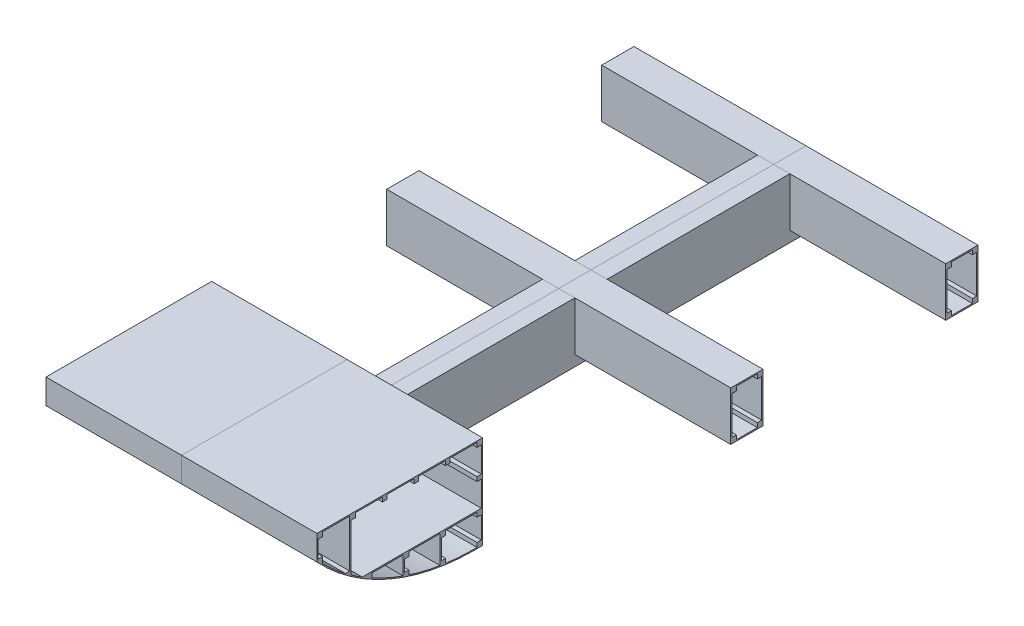
SolidWorks part; units mm, degrees
ref_plane "Front Plane" through (0, 0, 0) normal (0, 0, 1) x (1, 0, 0)
ref_plane "Top Plane" through (0, 0, 0) normal (0, 1, 0) x (1, 0, 0)
ref_plane "Right Plane" through (0, 0, 0) normal (1, 0, 0) x (0, 0, -1)
sketch "Sketch1" plane through (0, 0, 0) normal (1, 0, 0) x (0, 0, -1)
  line L0 (5334, 765) -> (5334, 309) construction
  line L1 (5184, 765) -> (5484, 765)
  line L2 (5184, 765) -> (5184, 309)
  line L3 (5184, 309) -> (5484, 309)
  line L4 (5484, 765) -> (5484, 309)
  line L5 (7184, 765) -> (7484, 765)
  line L6 (7184, 765) -> (7184, 309)
  line L7 (7184, 309) -> (7484, 309)
  line L8 (7484, 765) -> (7484, 309)
  line L9 (7184, 537) -> (7484, 537) construction
  line L10 (5184, 537) -> (5484, 537) construction
  line L11 (7334, 765) -> (7334, 309) construction
  line L12 (7432, 753) -> (7236, 753)
  line L13 (7236, 753) -> (7236, 713)
  line L14 (7236, 713) -> (7196, 713)
  line L15 (7196, 713) -> (7196, 361)
  line L16 (5432, 753) -> (5236, 753)
  line L17 (5236, 753) -> (5236, 713)
  line L18 (5236, 713) -> (5196, 713)
  line L19 (5196, 713) -> (5196, 361)
  line L20 (5472, 713) -> (5472, 361)
  line L21 (5432, 713) -> (5472, 713)
  line L22 (5432, 753) -> (5432, 713)
  line L23 (5236, 361) -> (5196, 361)
  line L24 (5236, 321) -> (5236, 361)
  line L25 (5432, 321) -> (5236, 321)
  line L26 (5432, 321) -> (5432, 361)
  line L27 (5432, 361) -> (5472, 361)
  line L28 (7472, 713) -> (7472, 361)
  line L29 (7432, 713) -> (7472, 713)
  line L30 (7432, 753) -> (7432, 713)
  line L31 (7236, 361) -> (7196, 361)
  line L32 (7236, 321) -> (7236, 361)
  line L33 (7432, 321) -> (7236, 321)
  line L34 (7432, 321) -> (7432, 361)
  line L35 (7432, 361) -> (7472, 361)
  line L36 (7500.6785, 309) -> (3141.2111, 309) construction
  line L37 (5184, 758.7422) -> (5184, 309) construction
  line L38 (5184, 765) -> (7500, 765) construction
  line L39 (7500.4262, 765) -> (5543.6931, 765) construction
  line L40 (7484, 759) -> (7484, -100) construction
  point P30 (5334, 753)
  point P31 (5196, 537)
  point P36 (5472, 537)
  point P37 (0, 0)
  point P40 (7334, 753)
  point P41 (7196, 537)
  point P46 (7472, 537)
  point P51 (7464.8091, 765)
  dimension "D1" = 12
  dimension "D2" = 12
  dimension "D3" = 40
  dimension "D4" = 12
  dimension "D5" = 300
  dimension "D7" = 1700
extrude "Boss-Extrude1" add sketch "Sketch1" along normal blind 1600
sketch "Sketch3" plane through (0, 0, 0) normal (1, 0, 0) x (0, 0, -1)
  line L0 (1675, 1176.9786) -> (3216, 1176.9786)
  line L1 (3216, 309) -> (3216, 1205.7293) construction
  line L2 (3216, 1176.9786) -> (3216, 309)
  line L3 (3216, 309) -> (3141.2111, 309)
  line L4 (1675, 1176.9786) -> (1675, 946.193)
  line L5 (3164, 1164.9786) -> (3164, 1124.9786)
  line L6 (3164, 1124.9786) -> (3204, 1124.9786)
  line L7 (3204, 1124.9786) -> (3204, 889.9786)
  line L8 (3204, 889.9786) -> (3164, 889.9786)
  line L9 (3164, 889.9786) -> (3164, 849.9786)
  line L10 (3164, 849.9786) -> (3204, 849.9786)
  line L11 (3204, 849.9786) -> (3204, 614.9786)
  line L12 (3204, 614.9786) -> (2096.401, 614.9786)
  line L13 (3164, 1164.9786) -> (2911, 1164.9786)
  line L14 (2911, 1164.9786) -> (2911, 1124.9786)
  line L15 (2911, 1124.9786) -> (2871, 1124.9786)
  line L16 (2871, 1124.9786) -> (2871, 1164.9786)
  line L17 (2871, 1164.9786) -> (2618, 1164.9786)
  line L18 (2618, 1164.9786) -> (2618, 1124.9786)
  line L19 (2618, 1124.9786) -> (2578, 1124.9786)
  line L20 (2578, 1124.9786) -> (2578, 1164.9786)
  line L21 (2578, 1164.9786) -> (2325, 1164.9786)
  line L22 (2325, 1164.9786) -> (2325, 1124.9786)
  line L23 (2325, 1124.9786) -> (2285, 1124.9786)
  line L24 (2285, 1124.9786) -> (2285, 1164.9786)
  line L25 (2285, 1164.9786) -> (2032, 1164.9786)
  line L26 (2032, 1164.9786) -> (2032, 1124.9786)
  line L27 (2032, 1124.9786) -> (1992, 1124.9786)
  line L29 (1980, 1164.9786) -> (1727, 1164.9786)
  line L30 (1727, 1164.9786) -> (1727, 1124.9786)
  line L31 (1727, 1124.9786) -> (1687, 1124.9786)
  line L32 (1687, 1124.9786) -> (1687, 964.9786)
  line L33 (1687, 964.9786) -> (1727, 964.9786)
  line L34 (1727, 964.9786) -> (1727, 907.371)
  line L35 (3164, 602.9786) -> (2872.7112, 602.9786)
  line L36 (2872.7112, 602.9786) -> (2872.7112, 562.9786)
  line L37 (2872.7112, 562.9786) -> (2832.7112, 562.9786)
  line L38 (2832.7112, 562.9786) -> (2832.7112, 377.6578)
  line L39 (2832.7112, 377.6578) -> (2872.7112, 377.6578)
  line L40 (2872.7112, 377.6578) -> (2872.7112, 337.6578)
  line L41 (3164, 602.9786) -> (3164, 562.9786)
  line L42 (3164, 562.9786) -> (3204, 562.9786)
  line L43 (3204, 562.9786) -> (3204, 359.6372)
  line L44 (3204, 359.6372) -> (3164, 359.6372)
  line L45 (3164, 359.6372) -> (3164, 319.6372)
  line L46 (2820.7112, 602.9786) -> (2820.7112, 345.4198)
  line L47 (2820.7112, 602.9786) -> (2529.4224, 602.9786)
  line L48 (2529.4224, 602.9786) -> (2529.4224, 562.9786)
  line L49 (2529.4224, 562.9786) -> (2489.4224, 562.9786)
  line L50 (2489.4224, 562.9786) -> (2489.4224, 455.6286)
  line L51 (2489.4224, 455.6286) -> (2529.4224, 455.6286)
  line L52 (2529.4224, 455.6286) -> (2529.4224, 415.6286)
  line L53 (2477.4224, 433.1752) -> (2477.4224, 602.9786)
  line L54 (2477.4224, 602.9786) -> (2186.1335, 602.9786)
  line L55 (2186.1335, 602.9786) -> (2186.1335, 562.9786)
  line L56 (1980, 1164.9786) -> (1980, 721.6741)
  line L57 (1980, 721.6741) -> (1940, 721.6741)
  line L58 (1992, 1124.9786) -> (1992, 683.7591)
  arc A0 (3141.2111, 309) -> (1675, 946.193) centre (3141.2111, 2314.5071) cw
  arc A1 (2096.401, 614.9786) -> (1992, 683.7591) centre (3141.2111, 2314.5071) cw
  arc A2 (2872.7112, 337.6578) -> (3164, 319.6372) centre (3141.2111, 2314.5071) ccw
  arc A3 (2820.7112, 345.4198) -> (2529.4224, 415.6286) centre (3141.2111, 2314.5071) cw
  arc A4 (2477.4224, 433.1752) -> (2186.1335, 562.9786) centre (3141.2111, 2314.5071) cw
  arc A5 (1940, 721.6741) -> (1727, 907.371) centre (3141.2111, 2314.5071) cw
  arc A6 (1992, 683.7591) -> (1940, 721.6741) centre (3141.2111, 2314.5071) cw construction
  dimension "D5" = 2005.5071
  dimension "D6" = 1995
  dimension "D1" = 1541
  dimension "D2" = 12
  dimension "D3" = 12
  dimension "D4" = 12
  dimension "D7" = 40
  dimension "D8" = 160
  dimension "D9" = 550
  dimension "D10" = 1107.599
  dimension "D11" = 12
  dimension "D12" = 12
  dimension "D13" = 12
  dimension "D14" = 40
  dimension "D15" = 12
  dimension "D16" = 253
  dimension "D17" = 1212
  dimension "D18" = 40
extrude "Boss-Extrude2" add sketch "Sketch3" along normal blind 1260 separate body
sketch "Sketch4" plane through (0, 0, 0) normal (1, 0, 0) x (0, 0, -1)
  line L0 (7484, 309) -> (7184, 309)
  line L1 (7184, 309) -> (7184, 765)
  line L2 (7184, 765) -> (5484, 765)
  line L3 (5484, 765) -> (5484, 309)
  line L4 (5184, 309) -> (5184, 765)
  line L5 (5184, 765) -> (3216, 765)
  line L6 (3216, 309) -> (3216, 1176.9786) construction
  line L7 (3216, 765) -> (3216, 309)
  line L8 (3216, 309) -> (3141.2111, 309)
  line L9 (7484, 309) -> (7484, 109)
  line L10 (7484, 109) -> (3141.2111, 109)
  line L11 (2096.401, 602.6571) -> (2096.401, 552.6571)
  line L12 (3141.2111, 309) -> (3141.2111, 109) construction
  line L13 (5184, 309) -> (5484, 309)
  arc A0 (1675, 946.193) -> (3141.2111, 309) centre (3141.2111, 2314.5071) ccw construction
  arc A1 (1675, 946.193) -> (3141.2111, 309) centre (3141.2111, 2314.5071) ccw construction
  arc A2 (3141.2111, 309) -> (2096.401, 602.6571) centre (3141.2111, 2314.5071) cw
  arc A3 (3141.2111, 109) -> (2096.401, 552.6571) centre (3141.2111, 1561.0897) cw
  dimension "D1" = 200
  dimension "D2" = 50
extrude "Boss-Extrude3" add sketch "Sketch4" along normal blind 150 separate body contours L10 A3 L11 A2 L8 L7 L5 L4 L13 L3 L2 L1 L0 L9
chamfer "Chamfer1" distance 100 angle 45 2 edges at (150, 224.5084, -2573.6594) (150, 109, -5312.6056)
shell "Shell1" thickness 12 removed face at (0, 436.3554, -4822.4168)
mirror "Mirror1" about plane through (0, 0, 0) normal (1, 0, 0) of bodies 102 101 103 107
